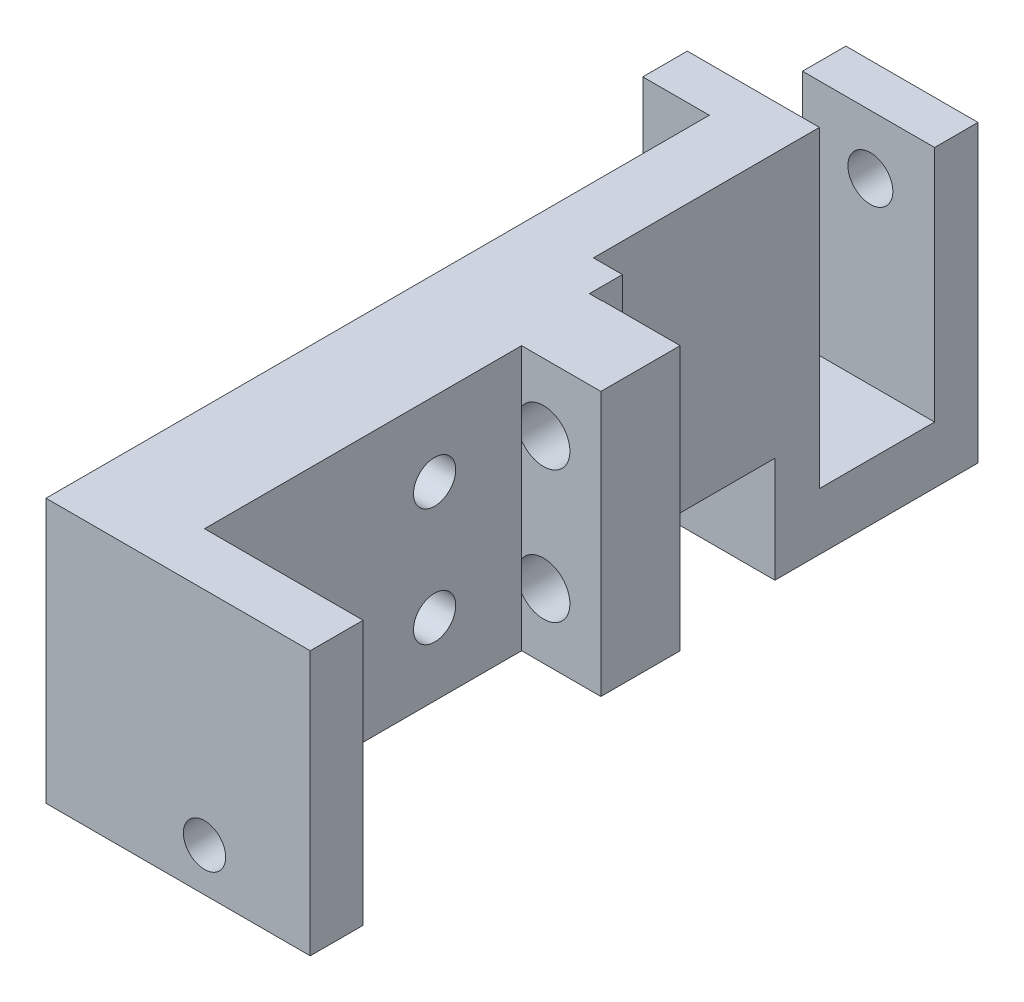
SolidWorks part; units mm, degrees
ref_plane "Front" through (0, 0, 0) normal (0, 0, 1) x (1, 0, 0)
ref_plane "Top" through (0, 0, 0) normal (0, 1, 0) x (1, 0, 0)
ref_plane "Right" through (0, 0, 0) normal (1, 0, 0) x (0, 0, -1)
sketch "Sketch1" plane through (0, 0, 0) normal (0, 1, 0) x (1, 0, 0)
  line L1 (0, 0) -> (8, 0)
  line L2 (0, 0) -> (0, -56.58)
  line L3 (0, -56.58) -> (8, -56.58)
  line L4 (8, 0) -> (8, -56.58)
  line L5 (0, -26.58) -> (14, -26.58)
  line L6 (0, -26.58) -> (0, -32.58)
  line L7 (0, -32.58) -> (14, -32.58)
  line L8 (14, -26.58) -> (14, -32.58)
  line L9 (0, -56.58) -> (20, -56.58)
  line L10 (0, -56.58) -> (0, -60.58)
  line L11 (0, -60.58) -> (20, -60.58)
  line L12 (20, -56.58) -> (20, -60.58)
  dimension "D1" = 24
  dimension "D2" = 6
  dimension "D3" = 6
  dimension "D4" = 8
  dimension "D5" = 4
  dimension "D6" = 20
  dimension "D7" = 56.58
extrude "Boss-Extrude1" add sketch "Sketch1" along normal blind 20 contours L7 L2 L3 L4 | L2 L7 L4 L5 | L2 L5 L4 L1 | L8 L5 L4 L7 | L12 L9 L3 L10 L11 region at (4, 0, 13.29) region at (4, 0, 29.58) region at (11, 0, 29.58) region at (4, 0, 44.58) region at (10, 0, 58.58)
sketch "Sketch2" plane through (0, 0, 0) normal (0, -1, 0) x (-1, 0, 0)
  line L0 (-7.4058, -24.1058) -> (-8.9058, -24.1058) construction
  line L1 (-8.1558, -24.1058) -> (-5.3536, -24.1058)
  line L2 (-8.1558, -24.1058) -> (-8.1558, 0.2442)
  line L3 (-8.1558, 0.2442) -> (-5.3536, 0.2442)
  line L4 (-5.3536, -24.1058) -> (-5.3536, 0.2442)
  line L6 (-8.1558, -24.1058) -> (-7.1558, -24.1058)
  line L7 (-8.1558, -24.1058) -> (-8.1558, -26.6058)
  line L8 (-8.1558, -26.6058) -> (-7.1558, -26.6058)
  line L9 (-7.1558, -24.1058) -> (-7.1558, -26.6058)
  line L10 (-5.3536, 0.2442) -> (-4.9638, 0.2442)
  line L11 (-5.3536, 0.2442) -> (-5.3536, -24.1058)
  line L12 (-5.3536, -24.1058) -> (-4.9638, -24.1058)
  line L13 (-4.9638, 0.2442) -> (-4.9638, -24.1058)
  line M6 (0, 0) -> (-8, 0)
  line M7 (-8, 0) -> (-8, -26.58)
  line M8 (-8, -26.58) -> (-14, -26.58)
  dimension "D1" = 2.5
  dimension "D2" = 1
extrude "Cut-Extrude1" cut sketch "Sketch2" against normal blind 20 contours L9 L1 L7 L8 M7 M8 | L1 L4 M6 M7 | L13 L4 L12 M6 region at (6.6768, 0, 12.0529) region at (7.5789, 0, 25.3582) region at (5.1587, 0, 12.0529)
sketch "Sketch3" plane through (0, 0, 0) normal (0, 0, -1) x (-1, 0, 0)
  line L1 (19.612, -22.3932) -> (-22.8928, -22.3932)
  line L2 (19.612, -22.3932) -> (19.612, 38.8779)
  line L3 (19.612, 38.8779) -> (-22.8928, 38.8779)
  line L4 (-22.8928, -22.3932) -> (-22.8928, 38.8779)
extrude "Cut-Extrude2" cut sketch "Sketch3" against normal blind 7
sketch "Sketch5" plane through (0, 0, 0) normal (0, -1, 0) x (-1, 0, 0)
  line L1 (-4.9638, -7) -> (5.0362, -7)
  line L2 (-4.9638, -7) -> (-4.9638, -10.373)
  line L3 (-4.9638, -10.373) -> (5.0362, -10.373)
  line L4 (5.0362, -7) -> (5.0362, -10.373)
extrude "Boss-Extrude3" add sketch "Sketch5" against normal blind 20 and the other way blind 8
sketch "Sketch6" plane through (0, 0, 26.58) normal (0, 0, -1) x (-1, 0, 0)
  circle A0 centre (-9.6558, 4.9046) radius 2
  circle A1 centre (-9.6558, 14.9046) radius 2
extrude "Cut-Extrude3" cut sketch "Sketch6" against normal blind 6
sketch "Sketch7" plane through (0, 0, 7) normal (0, 0, -1) x (-1, 0, 0)
  line L0 (5.0362, -8) -> (5.0362, 20) construction
  line L1 (-4.9638, -8) -> (5.0362, -8)
  line L2 (-4.9638, -8) -> (-4.9638, -3.6743)
  line L3 (-4.9638, -3.6743) -> (5.0362, -3.6743)
  line L4 (5.0362, -8) -> (5.0362, -3.6743)
extrude "Boss-Extrude4" add sketch "Sketch7" along normal blind 12
sketch "Sketch8" plane through (0, -3.6743, 0) normal (0, 1, 0) x (1, 0, 0)
  line L0 (-5.0362, 5) -> (-5.0362, -7) construction
  line L1 (4.9638, 5) -> (-5.0362, 5)
  line L2 (4.9638, 5) -> (4.9638, 1.7149)
  line L3 (4.9638, 1.7149) -> (-5.0362, 1.7149)
  line L4 (-5.0362, 5) -> (-5.0362, 1.7149)
extrude "Boss-Extrude5" add sketch "Sketch8" along normal blind 18
sketch "Sketch9" plane through (0, 0, -5) normal (0, 0, -1) x (-1, 0, 0)
  circle A0 centre (-0.1027, 9.8606) radius 1.7
extrude "Cut-Extrude4" cut sketch "Sketch9" against normal blind 20
sketch "Sketch10" plane through (0, 0, 0) normal (-1, 0, 0) x (0, 0, 1)
  line L0 (10.373, 0) -> (10.373, 8.1637) construction
  line L1 (10.373, 7) -> (15.0312, 7)
  line L2 (10.373, 7) -> (10.373, 12.7)
  line L3 (10.373, 12.7) -> (15.0312, 12.7)
  line L4 (15.0312, 7) -> (15.0312, 12.7)
  line L5 (10.373, 0) -> (60.58, 0) construction
  dimension "D1" = 5.7
  dimension "D2" = 7
extrude "Cut-Extrude5" cut sketch "Sketch10" against normal blind 3
sketch "Sketch12" plane through (0, 0, 60.58) normal (0, 0, 1) x (1, 0, 0)
  line L0 (20, 20) -> (20, 0) construction
  circle A0 centre (12, 3.2655) radius 1.6
  dimension "D1" = 8
extrude "Cut-Extrude7" cut sketch "Sketch12" against normal blind 5
sketch "Sketch13" plane through (0, 0, 0) normal (-1, 0, 0) x (0, 0, 1)
  circle A0 centre (39.1672, 5.4688) radius 1.6
  circle A1 centre (39.1672, 14.3708) radius 1.6
extrude "Cut-Extrude8" cut sketch "Sketch13" against normal blind 12
